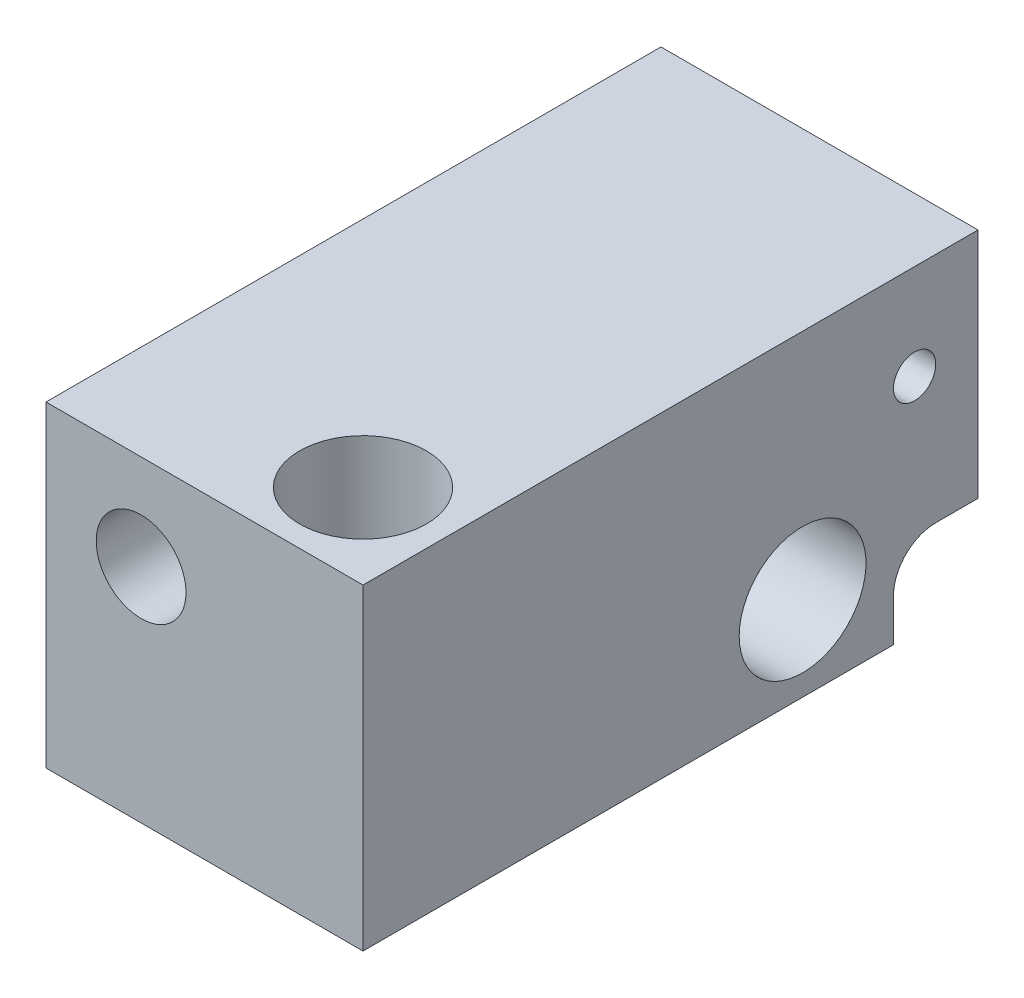
SolidWorks part; units mm, degrees
material "Lega 1060"
ref_plane "Piano frontale" through (0, 0, 0) normal (0, 0, 1) x (1, 0, 0)
ref_plane "Piano superiore" through (0, 0, 0) normal (0, 1, 0) x (1, 0, 0)
ref_plane "Piano destro" through (0, 0, 0) normal (1, 0, 0) x (0, 0, -1)
sketch "Schizzo1" plane through (0, 0, 0) normal (0, 0, 1) x (1, 0, 0)
  line L1 (0, 0) -> (30, 0)
  line L2 (0, 0) -> (0, 30)
  line L3 (0, 30) -> (30, 30)
  line L4 (30, 0) -> (30, 30)
  dimension "D1" = 30
extrude "Estrusione-Estrusione1" add sketch "Schizzo1" along normal blind 58.2
sketch "Schizzo2" plane through (0, 0, 0) normal (0, -1, 0) x (1, 0, 0)
  line L1 (0, 58.2) -> (30, 58.2) construction
  line L3 (30, 58.2) -> (30, 0) construction
  circle A0 centre (22, 50.2) radius 6
  dimension "D1" = 12
  dimension "D3" = 2
  dimension "D2" = 2
extrude "Taglio-Estrusione1" cut sketch "Schizzo2" against normal up to next
ref_point "Punto1"
sketch "Schizzo3" plane through (0, 0, 0) normal (-1, 0, 0) x (0, 0, 1)
  line L0 (50.2, 0) -> (50.2, 8) construction
  line L1 (50.2, 8) -> (16.6, 8) construction
  line L3 (58.2, 0) -> (0, 0) construction
  circle A0 centre (16.6, 8) radius 6
  dimension "D1" = 12
  dimension "D3" = 2
  dimension "D2" = 33.6
extrude "Taglio-Estrusione2" cut sketch "Schizzo3" against normal up to next
sketch "Schizzo5" plane through (0, 0, 0) normal (0, 0, -1) x (-1, 0, 0)
  line L0 (0, 30) -> (-30, 0) construction
  line L1 (0, 30) -> (0, 0) construction
  line L2 (-30, 30) -> (0, 30) construction
  circle A0 centre (-9, 21) radius 7
  dimension "D1" = 14
  dimension "D2" = 9
  dimension "D3" = 9
extrude "Taglio-Estrusione3" cut sketch "Schizzo5" against normal blind 20
hole_wizard "Foro Ø6.0 (6)-1" positions "Schizzo7" profile "Schizzo6" hole size "Ø6.0" standard "ISO" end condition up to next
sketch "Schizzo7" plane through (0, 0, 58.2) normal (0, 0, 1) x (1, 0, 0)
  line L0 (0, 30) -> (30, 0) construction
  line L2 (0, 0) -> (30, 0) construction
  line L3 (30, 0) -> (30, 30) construction
  line L4 (0, 30) -> (0, 0) construction
  line L5 (30, 30) -> (0, 30) construction
  circle A1 centre (9, 21) radius 7 construction
  point P0 (9, 21)
  dimension "D1" = 14
  dimension "D2" = 2
  dimension "D3" = 9
sketch "Schizzo6" plane through (9, 21, 58.2) normal (1, 0, 0) x (0, -1, 0)
  line L0 (0, 0) -> (0, 38.2)
  line L1 (0, 38.2) -> (3, 38.2)
  line L2 (3, 38.2) -> (3, 0)
  line L5 (3, 0) -> (0, 0)
  line L11 (0, -6.35) -> (0, 107.95) construction
  dimension "Thru Hole Dia." = 6
  dimension "Thru Hole Depth" = 38.2
hole_wizard "Foro Ø8.5 (8.5)-1" positions "Schizzo3D1" profile "Schizzo8" hole size "Ø8.5" standard "ISO"
sketch3d "Schizzo3D1"
  line L0 (9, 21, 20) -> (9, 21, 58.2) construction
  point P0 (9, 21, 58.2)
sketch "Schizzo8" plane through (9, 21, 58.2) normal (1, 0, 0) x (0, -1, 0)
  line L0 (0, 0) -> (0, 10.5537)
  line L1 (0, 10.5537) -> (4.25, 8)
  line L2 (4.25, 8) -> (4.25, 0)
  line L5 (4.25, 0) -> (0, 0)
  line L10 (0, 10.5537) -> (-4.25, 8) construction
  line L11 (0, -6.35) -> (0, 107.95) construction
  dimension "Hole Dia." = 8.5
  dimension "Hole Depth" = 8
  dimension "Drill Angle" = 118
hole_wizard "Foro filettato M3-1" positions "Schizzo10" profile "Schizzo9" tap size "M3" standard "ISO" end condition up to next
sketch "Schizzo10" plane through (30, 0, 0) normal (1, 0, 0) x (0, 0, -1)
  line L0 (0, 0) -> (0, 30) construction
  line L1 (-6, 21) -> (-10.6716, 21) construction
  line L4 (-58.2, 30) -> (0, 30) construction
  point P0 (-6, 21)
  dimension "D1" = 6
  dimension "D2" = 9
cosmetic thread "Filettatura del foro1" parameters "D2"=3
sketch "Schizzo9" plane through (30, 21, 6) normal (0, 1, 0) x (0, 0, -1)
  line L0 (0, 0) -> (0, 14)
  line L1 (0, 14) -> (1.25, 14)
  line L2 (1.25, 14) -> (1.25, 0)
  line L5 (1.25, 0) -> (0, 0)
  line L11 (0, -6.35) -> (0, 107.95) construction
  dimension "Thru Tap Drill Dia." = 2.5
  dimension "Thru Tap Drill Depth" = 14
hole_wizard "Foro Ø4.0 (4)-2" positions "Schizzo14" profile "Schizzo13" hole size "Ø4.0" standard "ISO"
sketch "Schizzo14" plane through (30, 0, 0) normal (1, 0, 0) x (0, 0, -1)
  point P0 (-6, 21)
sketch "Schizzo13" plane through (30, 21, 6) normal (0, 1, 0) x (0, 0, -1)
  line L0 (0, 0) -> (0, 9.2017)
  line L1 (0, 9.2017) -> (2, 8)
  line L2 (2, 8) -> (2, 0)
  line L5 (2, 0) -> (0, 0)
  line L10 (0, 9.2017) -> (-2, 8) construction
  line L11 (0, -6.35) -> (0, 107.95) construction
  dimension "Hole Dia." = 4
  dimension "Hole Depth" = 8
  dimension "Drill Angle" = 118
sketch "Schizzo17" plane through (0, 0, 0) normal (0, -1, 0) x (1, 0, 0)
  line L0 (0, 0) -> (30, 0) construction
  line L1 (7.5, 0) -> (11.5, 0)
  line L2 (7.5, 0) -> (7.5, 8)
  line L3 (7.5, 8) -> (11.5, 8)
  line L4 (11.5, 0) -> (11.5, 8)
  line L5 (15, 58.2) -> (15, 0) construction
  line L6 (0, 58.2) -> (30, 58.2) construction
  line L7 (18.5, 0) -> (18.5, 8)
  line L8 (22.5, 8) -> (18.5, 8)
  line L9 (22.5, 0) -> (22.5, 8)
  line L10 (22.5, 0) -> (18.5, 0)
  dimension "D1" = 4
  dimension "D2" = 8
  dimension "D3" = 3.5
sketch "Schizzo18" plane through (0, 0, 0) normal (0, -1, 0) x (1, 0, 0)
  line L0 (0, 0) -> (30, 0) construction
  line L1 (0, 0) -> (11.5, 0)
  line L2 (0, 0) -> (0, 8)
  line L3 (0, 8) -> (7.5, 8)
  line L4 (11.5, 0) -> (11.5, 4)
  line L5 (30, 58.2) -> (30, 0) construction
  line L6 (18.5, 0) -> (30, 0)
  line L7 (18.5, 0) -> (18.5, 4)
  line L8 (22.5, 8) -> (30, 8)
  line L9 (30, 0) -> (30, 8)
  arc A0 (7.5, 8) -> (11.5, 4) centre (7.5, 4) cw
  arc A1 (22.5, 8) -> (18.5, 4) centre (22.5, 4) ccw
  dimension "D1" = 4
sketch "Schizzo20" plane through (0, 0, 0) normal (-1, 0, 0) x (0, 0, 1)
  line L0 (4, 8) -> (0, 8)
  line L1 (0, 0) -> (8, 0) construction
  line L2 (0, 0) -> (0, 8) construction
  line L3 (0, 8) -> (8, 8) construction
  line L4 (8, 0) -> (8, 8) construction
  line L5 (0, 8) -> (0, 0)
  line L6 (0, 0) -> (8, 0)
  line L7 (8, 0) -> (8, 4)
  arc A1 (8, 4) -> (4, 8) centre (4, 4) ccw
  dimension "D1" = 8
  dimension "D2" = 8
  dimension "D3" = 8
extrude "Taglio-Estrusione5" cut sketch "Schizzo20" against normal blind 11.5
sketch "Schizzo21" plane through (30, 0, 0) normal (1, 0, 0) x (0, 0, -1)
  line L0 (-8, 0) -> (-8, 4) construction
  line L1 (0, 0) -> (-8, 0) construction
  line L2 (-4, 8) -> (0, 8) construction
  line L3 (0, 8) -> (0, 0) construction
  line L4 (-8, 0) -> (-8, 4)
  line L5 (0, 0) -> (-8, 0)
  line L6 (-4, 8) -> (0, 8)
  line L7 (0, 8) -> (0, 0)
  arc A0 (-4, 8) -> (-8, 4) centre (-4, 4) ccw construction
  arc A1 (-4, 8) -> (-8, 4) centre (-4, 4) ccw
extrude "Taglio-Estrusione6" cut sketch "Schizzo21" against normal blind 11.5
sketch "Schizzo23" plane through (11.5, 0, 0) normal (-1, 0, 0) x (0, 0, 1)
  circle A0 centre (3.6, 3.6) radius 1.6
extrude "Taglio-Estrusione7" cut sketch "Schizzo23" against normal up to surface (7 mm away) up to face at (18.5, 4.1657, 4.1657)
sketch "Schizzo24" plane through (0, 0, 20) normal (0, 0, -1) x (-1, 0, 0)
  circle A0 centre (-9, 21) radius 3
  circle A1 centre (-9, 21) radius 7
extrude "Estrusione-Estrusione2" add sketch "Schizzo24" along normal blind 7
